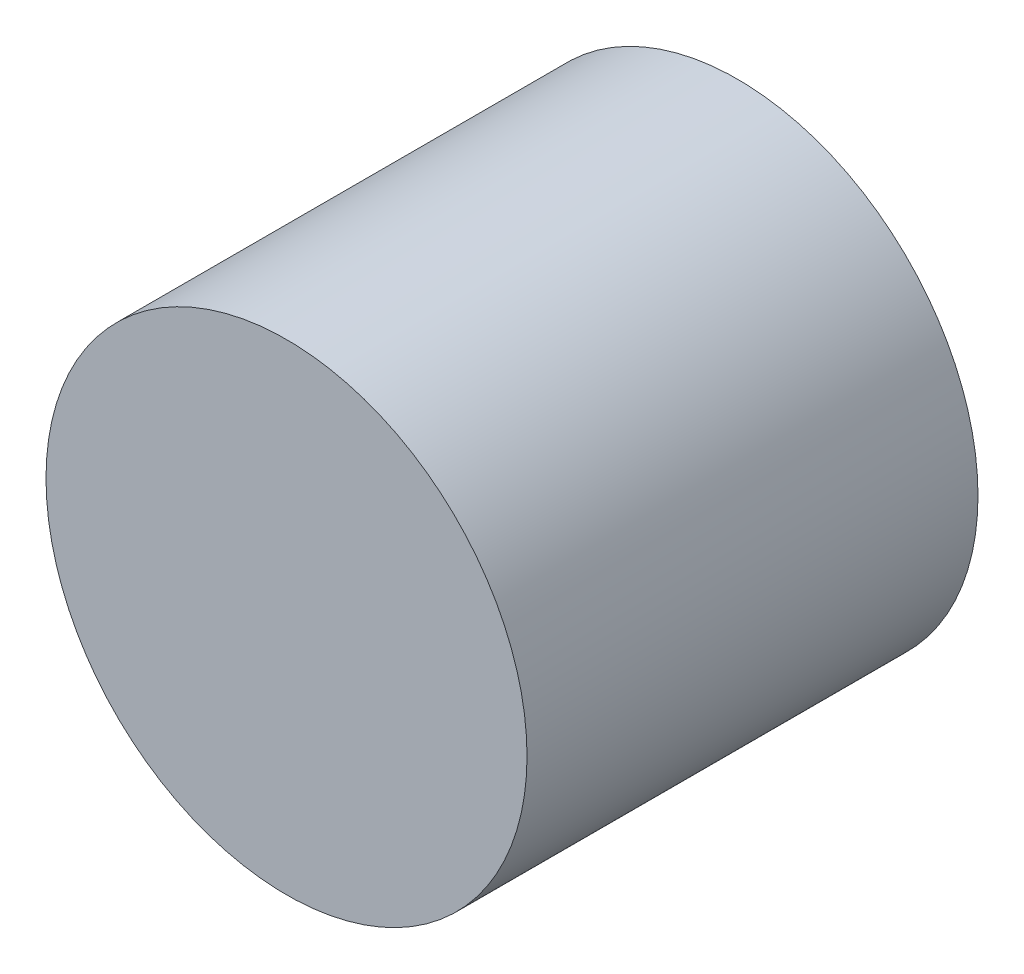
SolidWorks part; units mm, degrees
ref_plane "前视基准面" through (0, 0, 0) normal (0, 0, 1) x (1, 0, 0)
ref_plane "上视基准面" through (0, 0, 0) normal (0, 1, 0) x (1, 0, 0)
ref_plane "右视基准面" through (0, 0, 0) normal (1, 0, 0) x (0, 0, -1)
other "Configuration Table"
sketch "草图1" plane through (0, 0, 0) normal (0, 0, 1) x (1, 0, 0)
  circle A0 centre (0, 0) radius 16
extrude "凸台-拉伸1" add sketch "草图1" along normal mid plane 30
